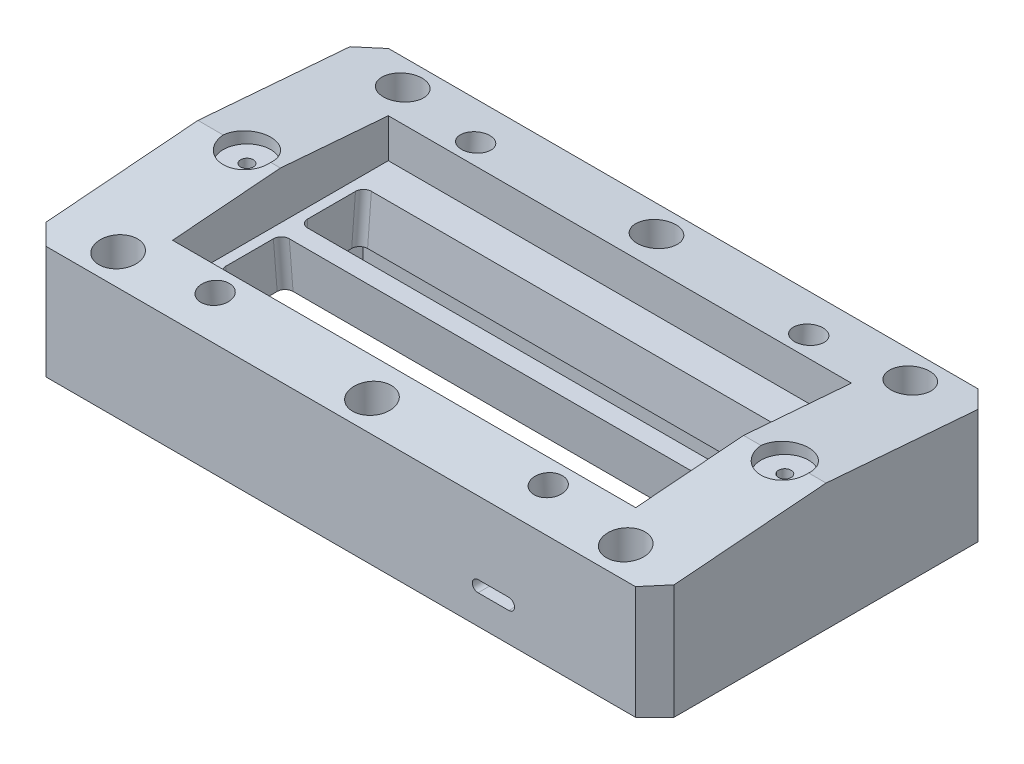
SolidWorks part; units mm, degrees
material "Custom Plastic"
ref_plane "Front Plane" through (0, 0, 0) normal (0, 0, 1) x (1, 0, 0)
ref_plane "Top Plane" through (0, 0, 0) normal (0, 1, 0) x (1, 0, 0)
ref_plane "Right Plane" through (0, 0, 0) normal (1, 0, 0) x (0, 0, -1)
sketch "Sketch1" plane through (0, 0, 0) normal (0, 1, 0) x (1, 0, 0)
  line L1 (0, 0) -> (198, 0)
  line L2 (0, 0) -> (0, 108)
  line L3 (0, 108) -> (198, 108)
  line L4 (198, 0) -> (198, 108)
  dimension "D1" = 198
  dimension "D2" = 108
extrude "Boss-Extrude1" add sketch "Sketch1" along normal blind 40
ref_plane "Left" through (198, 0, 0) normal (1, 0, 0) x (0, 0, -1)
ref_plane "Bot" through (0, 40, 0) normal (0, 1, 0) x (1, 0, 0)
ref_plane "der loco" through (0, 0, -52) normal (0, 0, -1) x (-1, 0, 0)
sketch "Sketch4" plane through (0, 0, 0) normal (0, 1, 0) x (1, 0, 0)
  line L0 (0, 108) -> (0, 0) construction
  line L1 (8.5, 31.5) -> (189.5, 31.5)
  line L2 (8.5, 31.5) -> (8.5, 76.5)
  line L3 (8.5, 76.5) -> (189.5, 76.5)
  line L4 (189.5, 31.5) -> (189.5, 76.5)
  line L5 (0, 0) -> (198, 0) construction
  dimension "D1" = 181
  dimension "D2" = 8.5
  dimension "D3" = 45
  dimension "D4" = 31.5
extrude "Cut-Extrude2" cut sketch "Sketch4" along normal blind 10 contours L2 L1 L4 L3
ref_plane "Plane32" through (0, 10, 0) normal (0, -1, 0) x (-1, 0, 0)
sketch "Sketch5" plane through (198, 0, 0) normal (1, 0, 0) x (0, 0, -1)
  line L0 (54, 40) -> (108, 35.6742)
  line L1 (0, 40) -> (108, 40) construction
  line L2 (108, 35.6742) -> (108, 40)
  line L3 (108, 40) -> (54, 40)
  line L4 (108, 40) -> (108, 0) construction
  dimension "D1" = 4.58
  dimension "D2" = 54
extrude "Cut-Extrude3" cut sketch "Sketch5" against normal up to vertex (198 mm away) up to point (0, 40, 0)
ref_plane "Plane24" through (0, 10, 0) normal (0, -1, 0) x (-1, 0, 0)
sketch "Sketch53" plane through (0, 10, 0) normal (0, -1, 0) x (-1, 0, 0)
  line L0 (-8.5, 51.5) -> (-8.5, 31.5)
  line L1 (-8.5, 76.5) -> (-8.5, 31.5) construction
  line L2 (-8.5, 31.5) -> (-39.5, 31.5)
  line L3 (-8.5, 31.5) -> (-189.5, 31.5) construction
  line L4 (-39.5, 31.5) -> (-8.5, 51.5)
  line L5 (-8.5, 54) -> (-189.5, 54) construction
  line L6 (-189.5, 31.5) -> (-189.5, 76.5) construction
  line L7 (-8.5, 56.5) -> (-8.5, 76.5)
  line L8 (-8.5, 76.5) -> (-39.5, 76.5)
  line L9 (-39.5, 76.5) -> (-8.5, 56.5)
  line L10 (-99, 76.5) -> (-99, 31.5) construction
  line L11 (-8.5, 76.5) -> (-189.5, 76.5) construction
  line L12 (-8.5, 31.5) -> (-189.5, 31.5) construction
  line L13 (-158.5, 76.5) -> (-189.5, 56.5)
  line L14 (-189.5, 76.5) -> (-158.5, 76.5)
  line L15 (-189.5, 56.5) -> (-189.5, 76.5)
  line L16 (-158.5, 31.5) -> (-189.5, 51.5)
  line L17 (-189.5, 31.5) -> (-158.5, 31.5)
  line L18 (-189.5, 51.5) -> (-189.5, 31.5)
  dimension "D1" = 31
  dimension "D2" = 20
extrude "Boss-Extrude11" add sketch "Sketch53" along normal up to surface (10 mm away) up to face at (99, 0, -54)
ref_plane "izq loco" through (0, 0, -57) normal (0, 0, -1) x (-1, 0, 0)
sketch "Sketch18" plane through (198, 0, 0) normal (1, 0, 0) x (0, 0, -1)
  line L0 (0, 35.6742) -> (0, 40)
  line L1 (0, 40) -> (0, 0) construction
  line L2 (0, 40) -> (54, 40)
  line L3 (54, 40) -> (0, 35.6742)
  line L4 (0, 40) -> (54, 40) construction
  dimension "D1" = 54
  dimension "D2" = 4.58
extrude "Cut-Extrude12" cut sketch "Sketch18" against normal up to surface (198 mm away) up to face at (0, 23.1348, -54)
sketch "Sketch60" plane through (0, 0, 0) normal (0, 1, 0) x (1, 0, 0)
  point P0 (8.5, 31.5)
  point P1 (39.5, 31.5)
  point P2 (8.5, 76.5)
  point P6 (39.5, 76.5)
  dimension "D1" = 20
  dimension "D2" = 31
  dimension "D3" = 20
  dimension "D4" = 31
ref_axis "Axis6" through (8.5, 0, -31.5) along (1, 0, 0)
sketch "Sketch69" plane through (0, 10, 0) normal (0, -1, 0) x (-1, 0, 0)
  point P0 (-39.5, 56.5)
  point P1 (-8.5, 51.5)
  point P2 (-38.5, 51.5)
  point P3 (-8.5, 56.5)
  dimension "D1" = 31
  dimension "D2" = 20
  dimension "D3" = 20
  dimension "D4" = 30
sketch "der loco axis" plane through (0, 0, -52) normal (0, 0, -1) x (-1, 0, 0)
  point P0 (-8.5, 8.5)
  point P1 (-38.5, 8.5)
  dimension "D1" = 1.5
sketch "izq loco axis" plane through (0, 0, -57) normal (0, 0, -1) x (-1, 0, 0)
  line L0 (-39.5, 0) -> (-39.5, 10) construction
  line L1 (-8.5, 0) -> (-8.5, 10) construction
  point P0 (-8.5, 8.4959)
  point P1 (-39.5, 8.4959)
  dimension "D1" = 1.5041
ref_plane "Plane3" through (0, 44.0431, -3.5282) normal (0, 0.9968, -0.0799) x (1, 0, 0)
ref_axis "Axis8" through (39.5, 0, -76.5) along (-1, 0, 0)
ref_axis "Axis9" through (8.5, 8.4959, -57) along (1, 0, 0)
ref_axis "Axis10" through (38.5, 8.5, -52) along (-1, 0, 0)
ref_plane "Izq bueno" through (0, 28.0127, -12.2048) normal (0, 0.9168, -0.3994) x (1, 0, 0)
sketch "Izq" plane through (0, 28.0127, -12.2048) normal (0, 0.9168, -0.3994) x (1, 0, 0)
  line L0 (8.5, 48.8622) -> (29.5, 70.1326)
  line L1 (29.5, 70.1326) -> (8.5, 70.1326)
  line L2 (8.5, 70.1326) -> (8.5, 48.8622)
  dimension "D1" = 21
extrude "Cut-Extrude28" cut sketch "Izq" against normal blind 14.5
ref_plane "Der bueno" through (0, -11.1449, -4.6211) normal (0, 0.9237, 0.383) x (1, 0, 0)
sketch "Der" plane through (0, -11.1449, -4.6211) normal (0, 0.9237, 0.383) x (1, 0, 0)
  line L0 (8.5, 51.2902) -> (29.5, 29.0979)
  line L1 (29.5, 29.0979) -> (8.5, 29.0979)
  line L2 (8.5, 29.0979) -> (8.5, 51.2902)
  dimension "D1" = 21
extrude "Cut-Extrude29" cut sketch "Der" against normal blind 14.5
sketch "Sketch97" plane through (0, 0, 0) normal (0, 1, 0) x (1, 0, 0)
  line L0 (8.5, 57.5) -> (29.5, 76.5)
  line L1 (29.5, 76.5) -> (158.5, 76.5)
  line L3 (158.5, 31.5) -> (29.5, 31.5)
  line L4 (29.5, 31.5) -> (8.5, 51.5)
  line L5 (8.5, 51.5) -> (8.5, 57.5)
  line L7 (158.5, 76.5) -> (189.5, 56.5)
  line L8 (189.5, 56.5) -> (189.5, 51.5)
  line L9 (189.5, 51.5) -> (158.5, 31.5)
  line L10 (39.5, 76.5) -> (158.5, 76.5) construction
  dimension "D1" = 6
extrude "Cut-Extrude40" cut sketch "Sketch97" along normal up to surface (10 mm away) up to face at (99, 10, -54)
ref_axis "Axis11" through (99, 0, -108) along (0, 0, 1)
ref_plane "Plane33" through (99, 0, 0) normal (1, 0, 0) x (0, 0, -1)
mirror "Mirror2" about plane through (99, 0, 0) normal (1, 0, 0) of "Cut-Extrude29", "Cut-Extrude40", "Cut-Extrude28"
sketch "Sketch6" plane through (0, 44.0431, -3.5282) normal (0, 0.9968, -0.0799) x (1, 0, 0)
  line L0 (0, 50.6335) -> (198, 50.6335) construction
  line L1 (28.9, 78.0335) -> (169.5, 78.0335)
  line L2 (25.9, 75.0335) -> (25.9, 54.4335)
  line L3 (28.9, 51.4335) -> (169.5, 51.4335)
  line L4 (172.5, 75.0335) -> (172.5, 54.4335)
  line L7 (28.6, 54.1335) -> (169.8, 54.1335)
  line L8 (28.6, 54.1335) -> (28.6, 75.3335)
  line L9 (28.6, 75.3335) -> (169.8, 75.3335)
  line L10 (169.8, 54.1335) -> (169.8, 75.3335)
  line L13 (198, 50.6335) -> (198, 104.8065) construction
  arc A0 (169.5, 78.0335) -> (172.5, 75.0335) centre (169.5, 75.0335) cw
  arc A1 (169.5, 51.4335) -> (172.5, 54.4335) centre (169.5, 54.4335) ccw
  arc A2 (25.9, 54.4335) -> (28.9, 51.4335) centre (28.9, 54.4335) ccw
  arc A3 (28.9, 78.0335) -> (25.9, 75.0335) centre (28.9, 75.0335) ccw
  dimension "D1" = 3
  dimension "D2" = 146.6
  dimension "D3" = 20.6
  dimension "D4" = 25.5
  dimension "D5" = 3.5
  dimension "D6" = 2.7
  dimension "D7" = 2.7
  dimension "D8" = 2.7
  dimension "D9" = 2.7
sketch "Sketch9" plane through (0, 40, 0) normal (0, 1, 0) x (1, 0, 0)
  line L1 (0, 54) -> (198, 54) construction
  circle A0 centre (15.45, 54) radius 8
  dimension "D1" = 16
  dimension "D2" = 15.45
sketch "Sketch12" plane through (0, 40, 0) normal (0, 1, 0) x (1, 0, 0)
  line L1 (0, 108) -> (198, 108) construction
  line L4 (0, 0) -> (198, 0) construction
  circle A0 centre (19.7, 98.85) radius 3.15
  circle A1 centre (99.7, 9.15) radius 3.15
  circle A2 centre (179.7, 9.15) radius 3.15
  circle A3 centre (19.7, 9.15) radius 3.15
  circle A4 centre (99.7, 98.85) radius 3.15
  circle A5 centre (179.7, 98.85) radius 3.15
  dimension "D1" = 9.15
  dimension "D2" = 6.3
  dimension "D3" = 9.15
  dimension "D4" = 19.7
  dimension "D7" = 80
  dimension "D9" = 80
extrude "Cut-Extrude9" cut sketch "Sketch12" against normal through all
sketch "Sketch13" plane through (0, 44.0431, -3.5282) normal (0, 0.9968, -0.0799) x (1, 0, 0)
  line L1 (0, 104.8065) -> (198, 104.8065) construction
  line L2 (198, 50.6335) -> (198, 104.8065) construction
  line L3 (0, 50.6335) -> (0, 104.8065) construction
  circle A0 centre (46.5, 91.8065) radius 4.5
  circle A1 centre (151.5, 91.8065) radius 4.5
  dimension "D1" = 9
  dimension "D4" = 9
  dimension "D2" = 46.5
  dimension "D3" = 13
  dimension "D5" = 46.5
extrude "Cut-Extrude10" cut sketch "Sketch13" against normal blind 16.5
sketch "Sketch14" plane through (0, 35.2123, 5.7666) normal (0, 0.9968, 0.0799) x (1, 0, 0)
  line L3 (198, 5.7851) -> (198, 59.9581) construction
  line L4 (0, 59.9581) -> (198, 59.9581) construction
  circle A0 centre (46.5, 18.7396) radius 4.5
  circle A1 centre (151.5, 18.7396) radius 4.5
  dimension "D1" = 9
  dimension "D2" = 9
  dimension "D3" = 46.5
  dimension "D4" = 41.2185
  dimension "D5" = 46.5
extrude "Cut-Extrude11" cut sketch "Sketch14" against normal blind 16.5
ref_plane "Plane9" through (0, 35.4468, 2.8395) normal (0, 0.9968, 0.0799) x (1, 0, 0)
sketch "Sketch23" plane through (0, 35.4468, 2.8395) normal (0, 0.9968, 0.0799) x (1, 0, 0)
  line L0 (0, 57.0216) -> (198, 57.0216) construction
  line L1 (28.9, 56.2216) -> (169.5, 56.2216)
  line L2 (25.9, 53.2216) -> (25.9, 32.6216)
  line L3 (28.9, 29.6216) -> (169.5, 29.6216)
  line L4 (172.5, 53.2216) -> (172.5, 32.6216)
  line L7 (28.6, 53.5216) -> (169.8, 53.5216)
  line L8 (28.6, 53.5216) -> (28.6, 32.3216)
  line L9 (28.6, 32.3216) -> (169.8, 32.3216)
  line L10 (169.8, 53.5216) -> (169.8, 32.3216)
  line L12 (198, 2.8486) -> (198, 57.0216) construction
  arc A0 (169.5, 56.2216) -> (172.5, 53.2216) centre (169.5, 53.2216) cw
  arc A1 (169.5, 29.6216) -> (172.5, 32.6216) centre (169.5, 32.6216) ccw
  arc A2 (25.9, 32.6216) -> (28.9, 29.6216) centre (28.9, 32.6216) ccw
  arc A3 (28.9, 56.2216) -> (25.9, 53.2216) centre (28.9, 53.2216) ccw
  point P10 (172.5, 56.2216)
  point P15 (25.9, 29.6216)
  point P18 (25.9, 56.2216)
  dimension "D5" = 3
  dimension "D1" = 146.6
  dimension "D2" = 20.6
  dimension "D3" = 3.5
  dimension "D4" = 25.5
  dimension "D6" = 2.7
  dimension "D7" = 2.7
  dimension "D8" = 2.7
  dimension "D9" = 2.7
sketch "Sketch41" plane through (0, 0, 0) normal (0, 1, 0) x (1, 0, 0)
  line L0 (198, 0) -> (198, 108) construction
  line L1 (198, 108) -> (0, 108) construction
  line L2 (0, 0) -> (198, 0) construction
  circle A0 centre (139.5, 9) radius 2.9
  circle A1 centre (139.5, 99) radius 2.9
  dimension "D1" = 5.8
  dimension "D4" = 5.8
  dimension "D2" = 58.5
  dimension "D3" = 58.5
  dimension "D5" = 9
  dimension "D6" = 9
extrude "Cut-Extrude21" cut sketch "Sketch41" along normal blind 7
sketch "Sketch42" plane through (0, 0, 0) normal (0, 0, 1) x (1, 0, 0)
  line L0 (198, 35.6742) -> (198, 0) construction
  line L5 (0, 0) -> (198, 0) construction
  line L6 (142.3, 12.8) -> (152, 12.8)
  line L7 (142.3, 9.2) -> (152, 9.2)
  arc A0 (142.3, 12.8) -> (142.3, 9.2) centre (142.3, 11) ccw
  arc A2 (152, 12.8) -> (152, 9.2) centre (152, 11) cw
  dimension "D2" = 1.8
  dimension "D3" = 1.8
  dimension "D1" = 9.7
  dimension "D5" = 46
  dimension "D6" = 11
extrude "Cut-Extrude22" cut sketch "Sketch42" against normal blind 10
ref_plane "Plane19" through (0, 0, -108) normal (0, 0, -1) x (-1, 0, 0)
sketch "Sketch43" plane through (0, 0, -108) normal (0, 0, -1) x (-1, 0, 0)
  line L0 (-55.7, 11) -> (-46, 11) construction
  line L1 (-55.7, 12.8) -> (-46, 12.8)
  line L2 (-55.7, 9.2) -> (-46, 9.2)
  line L3 (-198, 0) -> (0, 0) construction
  line L4 (0, 35.6742) -> (0, 0) construction
  arc A0 (-55.7, 12.8) -> (-55.7, 9.2) centre (-55.7, 11) ccw
  arc A1 (-46, 9.2) -> (-46, 12.8) centre (-46, 11) ccw
  point P2 (-50.85, 11)
  dimension "D2" = 1.8
  dimension "D1" = 9.7
  dimension "D3" = 11
  dimension "D4" = 46
extrude "Cut-Extrude23" cut sketch "Sketch43" against normal blind 10
sketch "Sketch84" plane through (0, 44.0431, -3.5282) normal (0, 0.9968, -0.0799) x (1, 0, 0)
  line L0 (0, 50.6335) -> (198, 50.6335) construction
  line L1 (31.7, 54.7335) -> (166.7, 54.7335)
  line L2 (29.2, 57.2335) -> (29.2, 72.2335)
  line L3 (31.7, 74.7335) -> (166.7, 74.7335)
  line L4 (169.2, 57.2335) -> (169.2, 72.2335)
  line L7 (0, 50.6335) -> (0, 104.8065) construction
  arc A0 (166.7, 54.7335) -> (169.2, 57.2335) centre (166.7, 57.2335) ccw
  arc A1 (166.7, 74.7335) -> (169.2, 72.2335) centre (166.7, 72.2335) cw
  arc A2 (29.2, 72.2335) -> (31.7, 74.7335) centre (31.7, 72.2335) cw
  arc A3 (31.7, 54.7335) -> (29.2, 57.2335) centre (31.7, 57.2335) cw
  point P10 (169.2, 54.7335)
  point P13 (169.2, 74.7335)
  point P16 (29.2, 74.7335)
  point P19 (169.2, 64.7335)
  dimension "D5" = 2.5
  dimension "D1" = 140
  dimension "D2" = 20
  dimension "D3" = 4.1
  dimension "D4" = 29.2
extrude "Cut-Extrude35" cut sketch "Sketch84" against normal blind 55.4
sketch "Sketch83" plane through (0, 35.4468, 2.8395) normal (0, 0.9968, 0.0799) x (1, 0, 0)
  line L1 (31.7, 52.9216) -> (166.7, 52.9216)
  line L2 (29.2, 50.4216) -> (29.2, 35.4216)
  line L3 (31.7, 32.9216) -> (166.7, 32.9216)
  line L4 (169.2, 50.4216) -> (169.2, 35.4216)
  line L7 (0, 57.0216) -> (198, 57.0216) construction
  line L8 (0, 57.0216) -> (0, 2.8486) construction
  arc A0 (166.7, 32.9216) -> (169.2, 35.4216) centre (166.7, 35.4216) ccw
  arc A1 (166.7, 52.9216) -> (169.2, 50.4216) centre (166.7, 50.4216) cw
  arc A2 (29.2, 35.4216) -> (31.7, 32.9216) centre (31.7, 35.4216) ccw
  arc A3 (31.7, 52.9216) -> (29.2, 50.4216) centre (31.7, 50.4216) ccw
  point P12 (169.2, 52.9216)
  point P15 (29.2, 32.9216)
  point P18 (29.2, 52.9216)
  point P19 (169.2, 42.9216)
  dimension "D5" = 2.5
  dimension "D1" = 140
  dimension "D2" = 20
  dimension "D3" = 29.2
  dimension "D4" = 4.1
extrude "Cut-Extrude34" cut sketch "Sketch83" against normal blind 55.4
sketch "Sketch85" plane through (0, 40, 0) normal (0, 1, 0) x (1, 0, 0)
  line L0 (0, 101.9) -> (6.1, 108)
  line L3 (6.1, 108) -> (0, 108)
  line L4 (0, 108) -> (0, 101.9)
  line L5 (0, 0) -> (6.1, 0)
  line L7 (6.1, 0) -> (0, 6.1)
  line L9 (0, 6.1) -> (0, 0)
  line L10 (198, 6.1) -> (191.9, 0)
  line L11 (198, 0) -> (198, 54) construction
  line L12 (0, 0) -> (198, 0) construction
  line L13 (191.9, 0) -> (198, 0)
  line L14 (198, 0) -> (198, 6.1)
  line L15 (198, 108) -> (191.9, 108)
  line L16 (0, 108) -> (198, 108) construction
  line L17 (191.9, 108) -> (198, 101.9)
  line L18 (198, 54) -> (198, 108) construction
  line L19 (198, 101.9) -> (198, 108)
  line L20 (0, 54) -> (0, 108) construction
  line L21 (0, 108) -> (198, 108) construction
  line L22 (0, 0) -> (198, 0) construction
  line L23 (0, 54) -> (0, 0) construction
  dimension "D1" = 6.1
  dimension "D2" = 6.1
  dimension "D3" = 6.1
  dimension "D4" = 6.1
  dimension "D5" = 6.1
  dimension "D6" = 6.1
  dimension "D7" = 6.1
extrude "Cut-Extrude36" cut sketch "Sketch85" against normal blind 55.4
sketch "Sketch90" plane through (0, 40, 0) normal (0, 1, 0) x (1, 0, 0)
  circle A0 centre (19.7, 9.15) radius 6.1
  circle A1 centre (99.7, 9.15) radius 6.1
  circle A2 centre (179.7, 9.15) radius 6.1
  circle A3 centre (99.7, 98.85) radius 6.1
  circle A4 centre (179.7, 98.85) radius 6.1
  circle A5 centre (19.7, 98.85) radius 6.1
  circle A6 centre (179.7, 98.85) radius 3.15 construction
  circle A7 centre (99.7, 98.85) radius 3.15 construction
  dimension "D1" = 12.2
  dimension "D2" = 3
  dimension "D3" = 2
extrude "Cut-Extrude38" cut sketch "Sketch90" against normal blind 17
sketch "Sketch96" plane through (0, 0, 0) normal (0, 1, 0) x (1, 0, 0)
  line L0 (0, 54) -> (198, 54) construction
  line L1 (198, 6.1) -> (198, 101.9) construction
  circle A0 centre (15.45, 54) radius 2
  circle A1 centre (185, 54) radius 2
  dimension "D1" = 4
  dimension "D2" = 4
  dimension "D3" = 13
extrude "Cut-Extrude39" cut sketch "Sketch96" along normal through all
sketch "Sketch98" plane through (0, 40, 0) normal (0, 1, 0) x (1, 0, 0)
  circle A0 centre (185, 54) radius 7.5
  circle A1 centre (15.45, 54) radius 7.5
  dimension "D1" = 15
  dimension "D2" = 15
extrude "Cut-Extrude41" cut sketch "Sketch98" against normal blind 4
sketch "Sketch99" plane through (198, 0, 0) normal (1, 0, 0) x (0, 0, -1)
  line L0 (57.4888, 39.7205) -> (78.6211, 38.0277) construction
  line L1 (54, -136.5975) -> (68.055, 38.8741) construction
  line L2 (54, -136.5975) -> (175.8472, -146.3583) construction
  line L3 (54, 40) -> (101.9, 36.1629) construction
  line L4 (54, -136.5975) -> (-67.8472, -146.3583) construction
  line L5 (6.1, 36.1629) -> (54, 40) construction
  line L6 (54.0015, -136.5975) -> (39.945, 38.8741) construction
  line L7 (-68.2375, -136.5975) -> (176.2375, -136.5975) construction
  line L8 (54, -136.5975) -> (39.945, 38.8741) construction
  line L9 (32.469, 38.2752) -> (47.4211, 39.473) construction
  line L10 (53.9985, -136.5975) -> (68.055, 38.8741) construction
  circle A0 centre (54, -136.5975) radius 122.2375
  point P19 (39.945, 38.8741)
  dimension "D1" = 244.475
  dimension "D2" = 136.5975
  dimension "D3" = 90
  dimension "D4" = 90
sketch "Croquis1" plane through (0, 40, 0) normal (0, 1, 0) x (1, 0, 0)
  line L0 (22.95, 54) -> (177.5, 54) construction
  line L1 (26, 20) -> (172, 20)
  line L2 (26, 20) -> (26, 88)
  line L3 (26, 88) -> (172, 88)
  line L4 (172, 20) -> (172, 88)
  line L5 (6.1, 108) -> (191.9, 108) construction
  line L6 (6.1, 0) -> (191.9, 0) construction
  line L7 (0, 54) -> (0, 101.9) construction
  point P4 (173.6, 22.5667)
  point P5 (172, 54)
  point P10 (173.6, 87.1796)
  point P11 (24.5643, 86.743)
  point P12 (99, 88)
  point P15 (99, 108)
  point P16 (172.126, 88.0527)
  dimension "D1" = 20
  dimension "D2" = 26
extrude "Cortar-Extruir1" cut sketch "Croquis1" against normal blind 15
